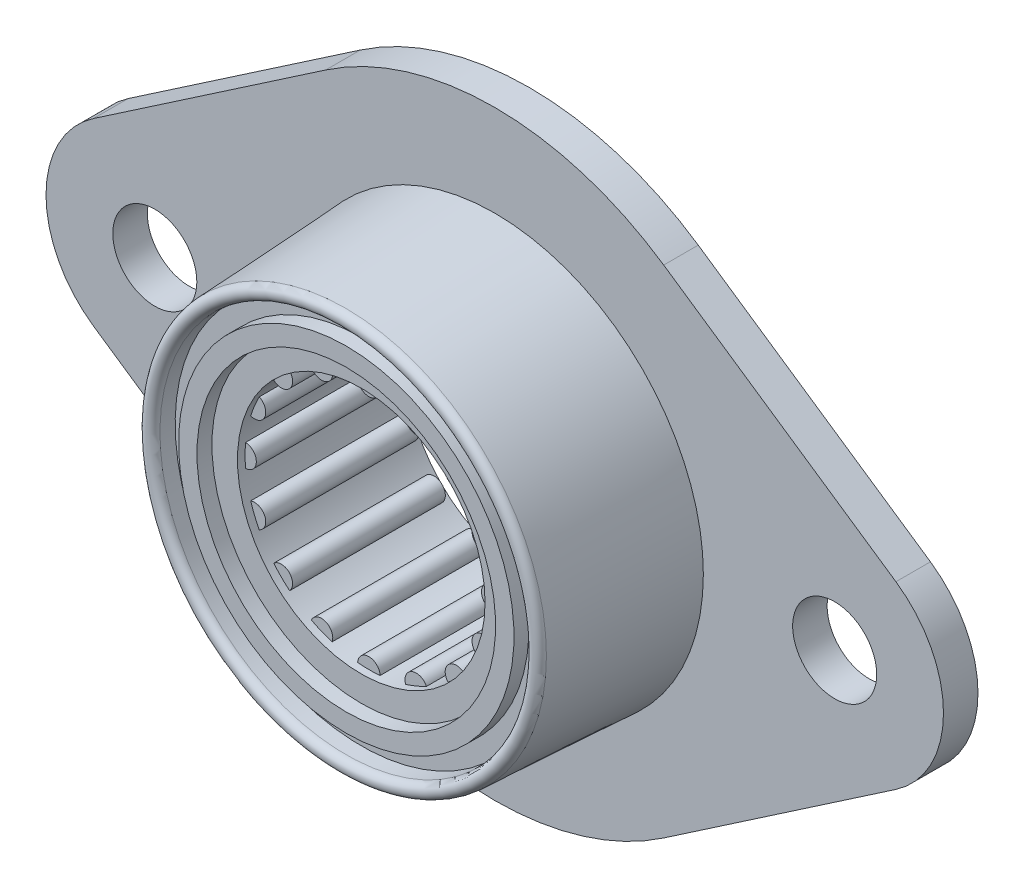
SolidWorks part; units mm, degrees
ref_plane "Front" through (0, 0, 0) normal (0, 0, 1) x (1, 0, 0)
ref_plane "Top" through (0, 0, 0) normal (0, 1, 0) x (1, 0, 0)
ref_plane "Right" through (0, 0, 0) normal (1, 0, 0) x (0, 0, -1)
sketch "Sketch1" plane through (0, 0, 0) normal (0, 0, 1) x (1, 0, 0)
  line L0 (0, 0) -> (-22.65, 0) construction
  line L1 (0, 0) -> (22.65, 0) construction
  line L2 (-26.7311, 5.9922) -> (-11.2583, 16.5303)
  line L3 (11.2583, 16.5303) -> (26.7311, 5.9922)
  line L4 (26.7311, -5.9922) -> (11.2583, -16.5303)
  line L5 (-11.2583, -16.5303) -> (-26.7311, -5.9922)
  line L6 (0, 20) -> (0, -20) construction
  arc A0 (11.2583, 16.5303) -> (-11.2583, 16.5303) centre (0, 0) ccw
  circle A1 centre (-22.65, 0) radius 2.8
  circle A2 centre (22.65, 0) radius 2.8
  arc A3 (26.7311, -5.9922) -> (26.7311, 5.9922) centre (22.65, 0) ccw
  arc A4 (-26.7311, 5.9922) -> (-26.7311, -5.9922) centre (-22.65, 0) ccw
  circle A5 centre (0, 0) radius 13.9
  arc A7 (-11.2583, -16.5303) -> (11.2583, -16.5303) centre (0, 0) ccw
  point P17 (0, 0)
  dimension "A" = 27.8
  dimension "Mounting Hole Dia" = 5.6
  dimension "Overall Length" = 59.8
  dimension "Mounting Holes" = 45.3
  dimension "Overall Height" = 40
extrude "Extrude1" add sketch "Sketch1" along normal blind 2.3
sketch "Sketch2" plane through (0, 0, 0) normal (1, 0, 0) x (0, 0, -1)
  line L0 (0, 13.9) -> (-2.3, 13.9)
  line L1 (-2.3, 13.9) -> (-12.2354, 13.3793)
  line L2 (-12.2097, 12.3994) -> (-11.1937, 12.3994)
  line L3 (-11.1937, 12.3994) -> (-11.1937, 11.1746)
  line L4 (-11.1937, 7.5) -> (0, 7.5)
  line L5 (0, 7.5) -> (0, 13.9)
  line L6 (-11.1937, 11.1746) -> (-12.192, 11.1746)
  line L7 (-12.192, 11.1746) -> (-12.192, 9.9497)
  line L8 (-12.192, 9.9497) -> (-11.1937, 9.9497)
  line L9 (-11.1937, 11.1746) -> (-11.1937, 9.9497) construction
  line L10 (0, 0) -> (-11.1937, 0) construction
  line L11 (-11.1937, 0) -> (-11.1937, 7.5) construction
  line L12 (-11.1937, 8.7249) -> (-11.1937, 7.5)
  line L13 (-11.1937, 9.9497) -> (-11.1937, 8.7249)
  line L14 (0, 16.5303) -> (0, 20) construction
  line L15 (0, 16.5303) -> (0, 20) construction
  line L16 (-12.2097, 12.8897) -> (-12.7, 12.8897) construction
  arc A0 (-12.2354, 13.3793) -> (-12.7, 12.8897) centre (-12.2097, 12.8897) ccw
  arc A1 (-12.7, 12.8897) -> (-12.2097, 12.3994) centre (-12.2097, 12.8897) ccw
  dimension "F" = 12.7
  dimension "Shaft Dia" = 15
  dimension "D3" = 0.9799
  dimension "D4" = 1.016
  dimension "D5" = 3
  dimension "D2" = 0.508
  dimension "D6" = 1.2249
revolve "Revolve1" add sketch "Sketch2" angle 360 about L10
sketch "Sketch3" plane through (0, 0, 11.1937) normal (0, 0, 1) x (1, 0, 0)
  line L0 (0, 0) -> (8.25, 0) construction
  arc A0 (-3.8363, 7.3038) -> (-5.2797, 6.3393) centre (0, 0) ccw
  arc A1 (8.2159, 0.7492) -> (8.2159, -0.7492) centre (8.25, 0) ccw
  circle A2 centre (0, 0) radius 7.5 construction
  arc A3 (7.8772, -2.4519) -> (7.3038, -3.8363) centre (7.622, -3.1571) ccw
  arc A4 (6.3393, -5.2797) -> (5.2797, -6.3393) centre (5.8336, -5.8336) ccw
  arc A5 (3.8363, -7.3038) -> (2.4519, -7.8772) centre (3.1571, -7.622) ccw
  arc A6 (0.7492, -8.2159) -> (-0.7492, -8.2159) centre (0, -8.25) ccw
  arc A7 (-2.4519, -7.8772) -> (-3.8363, -7.3038) centre (-3.1571, -7.622) ccw
  arc A8 (-5.2797, -6.3393) -> (-6.3393, -5.2797) centre (-5.8336, -5.8336) ccw
  arc A9 (-7.3038, -3.8363) -> (-7.8772, -2.4519) centre (-7.622, -3.1571) ccw
  arc A10 (-8.2159, -0.7492) -> (-8.2159, 0.7492) centre (-8.25, 0) ccw
  arc A11 (-7.8772, 2.4519) -> (-7.3038, 3.8363) centre (-7.622, 3.1571) ccw
  arc A12 (-6.3393, 5.2797) -> (-5.2797, 6.3393) centre (-5.8336, 5.8336) ccw
  arc A13 (-3.8363, 7.3038) -> (-2.4519, 7.8772) centre (-3.1571, 7.622) ccw
  arc A14 (-0.7492, 8.2159) -> (0.7492, 8.2159) centre (0, 8.25) ccw
  arc A15 (2.4519, 7.8772) -> (3.8363, 7.3038) centre (3.1571, 7.622) ccw
  arc A16 (5.2797, 6.3393) -> (6.3393, 5.2797) centre (5.8336, 5.8336) ccw
  arc A17 (7.3038, 3.8363) -> (7.8772, 2.4519) centre (7.622, 3.1571) ccw
  arc A18 (-6.3393, 5.2797) -> (-7.3038, 3.8363) centre (0, 0) ccw
  arc A19 (-7.8772, 2.4519) -> (-8.2159, 0.7492) centre (0, 0) ccw
  arc A20 (-8.2159, -0.7492) -> (-7.8772, -2.4519) centre (0, 0) ccw
  arc A21 (-7.3038, -3.8363) -> (-6.3393, -5.2797) centre (0, 0) ccw
  arc A22 (-5.2797, -6.3393) -> (-3.8363, -7.3038) centre (0, 0) ccw
  arc A23 (-2.4519, -7.8772) -> (-0.7492, -8.2159) centre (0, 0) ccw
  arc A24 (0.7492, -8.2159) -> (2.4519, -7.8772) centre (0, 0) ccw
  arc A25 (3.8363, -7.3038) -> (5.2797, -6.3393) centre (0, 0) ccw
  arc A26 (6.3393, -5.2797) -> (7.3038, -3.8363) centre (0, 0) ccw
  arc A27 (7.8772, -2.4519) -> (8.2159, -0.7492) centre (0, 0) ccw
  arc A28 (8.2159, 0.7492) -> (7.8772, 2.4519) centre (0, 0) ccw
  arc A29 (7.3038, 3.8363) -> (6.3393, 5.2797) centre (0, 0) ccw
  arc A30 (5.2797, 6.3393) -> (3.8363, 7.3038) centre (0, 0) ccw
  arc A31 (2.4519, 7.8772) -> (0.7492, 8.2159) centre (0, 0) ccw
  arc A32 (-0.7492, 8.2159) -> (-2.4519, 7.8772) centre (0, 0) ccw
  dimension "D1" = 16.5
extrude "Cut-Extrude2" cut sketch "Sketch3" against normal through all
sketch "Sketch4" plane through (0, 0, 11.1937) normal (0, 0, 1) x (1, 0, 0)
  circle A0 centre (0, 0) radius 8.25
extrude "Cut-Extrude3" cut sketch "Sketch4" against normal blind 0.508
sketch "Sketch5" plane through (0, 0, 0) normal (0, 0, -1) x (-1, 0, 0)
  circle A0 centre (0, 0) radius 8.25
  arc A1 (2.4519, 7.8772) -> (0.7492, 8.2159) centre (0, 0) ccw construction
extrude "Cut-Extrude4" cut sketch "Sketch5" against normal blind 0.508
sketch "Ref" plane through (0, 0, 0) normal (0, 0, 1) x (1, 0, 0)
  circle A0 centre (0, 0) radius 7.5
  dimension "Shaft Dia" = 15
ref_plane "Contact Plane 1" through (0, 0, 0) normal (0, 0, -1) x (-1, 0, 0)
ref_plane "Contact Plane 2" through (0, 0, 12.192) normal (0, 0, 1) x (1, 0, 0)
ref_plane "Contact Plane 3" through (0, 0, 2.3) normal (0, 0, 1) x (1, 0, 0)
ref_axis "Center Axis 1" through (0, 0, -0.635) along (0, 0, 1)
ref_axis "Center Axis 2" through (-22.65, 0, 2.3) along (0, 0, -1)
ref_axis "Center Axis 3" through (22.65, 0, 2.3) along (0, 0, -1)
equation "\"D1@Sketch3\"=\"Shaft Dia@Sketch2\"*1.1"
equation "\"D3@Sketch2\"=\"D6@Sketch2\"/1.25"
